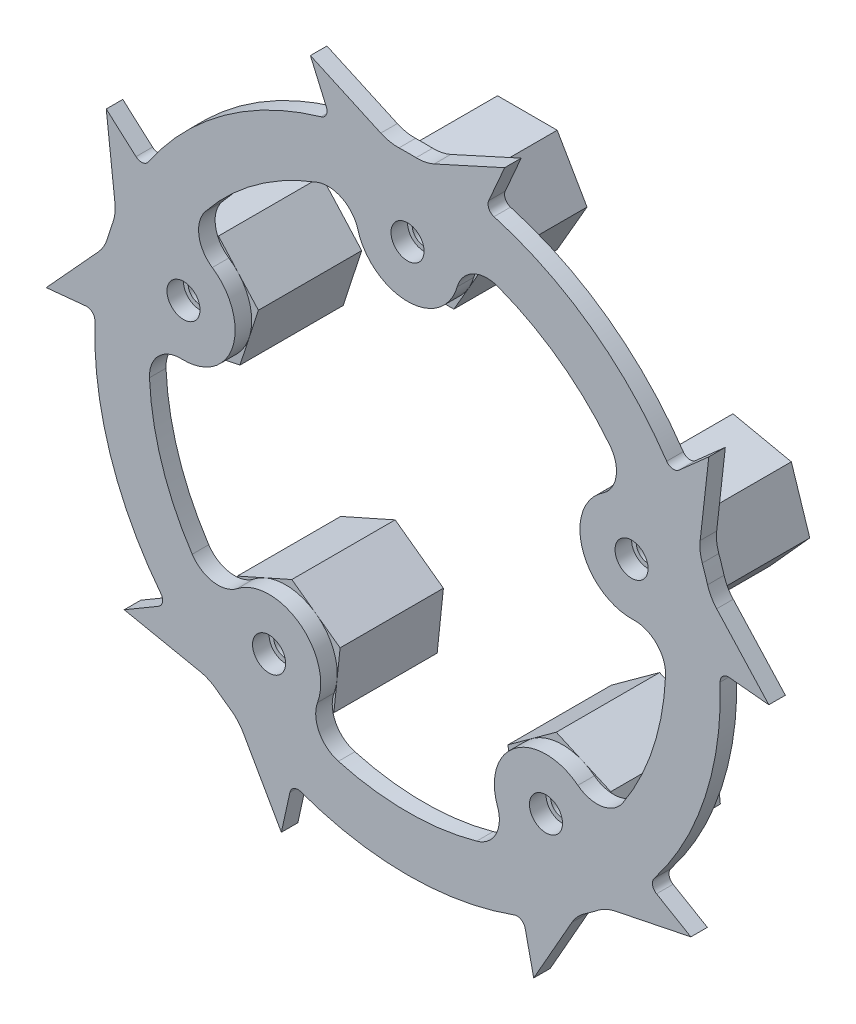
SolidWorks part; units mm, degrees
material "Alloy Steel (SS)"
ref_plane "Front Plane" through (0, 0, 0) normal (0, 0, 1) x (1, 0, 0)
ref_plane "Top Plane" through (0, 0, 0) normal (0, 1, 0) x (1, 0, 0)
ref_plane "Right Plane" through (0, 0, 0) normal (1, 0, 0) x (0, 0, -1)
sketch "Sketch1" plane through (0, 0, 0) normal (0, 0, 1) x (1, 0, 0)
  line L0 (0, 0) -> (0, 28.956) construction
  line L1 (0, 0) -> (27.5388, 8.9479) construction
  line L2 (0, 0) -> (17.0199, -23.4259) construction
  line L3 (0, 0) -> (-17.0199, -23.4259) construction
  line L4 (0, 0) -> (-27.5388, 8.9479) construction
  line L5 (-9.5106, 37.2552) -> (-11.938, 42.8169)
  line L6 (-11.938, 42.8169) -> (0, 0) construction
  line L7 (-11.938, 42.8169) -> (-3.2859, 38.8883)
  line L8 (0, 0) -> (0, 44.45) construction
  line L9 (9.5106, 37.2552) -> (11.938, 42.8169)
  line L10 (11.938, 42.8169) -> (3.2859, 38.8883)
  line L11 (-10.3266, 37.0373) -> (13.7805, 43.7588) construction
  line L12 (-11.938, 42.8169) -> (-5.2343, 44.686) construction
  circle A0 centre (0, 0) radius 44.45 construction
  circle A1 centre (0, 0) radius 31.75
  circle A2 centre (0, 28.956) radius 2.032
  arc A3 (6.1076, 27.2181) -> (-6.1076, 27.2181) centre (0, 28.956) cw
  arc A4 (6.1076, 27.2181) -> (11.1046, 29.7447) centre (9.7721, 26.1754) cw
  arc A5 (-6.1076, 27.2181) -> (-11.1046, 29.7447) centre (-9.7721, 26.1754) ccw
  arc A6 (23.9986, 14.2195) -> (24.8574, 19.7528) centre (21.8745, 17.3824) ccw
  arc A7 (27.7733, 2.6022) -> (23.9986, 14.2195) centre (27.5388, 8.9479) cw
  circle A8 centre (27.5388, 8.9479) radius 2.032
  arc A9 (27.7733, 2.6022) -> (31.7204, -1.3695) centre (27.914, -1.2052) cw
  arc A10 (20.9395, -18.43) -> (26.4674, -17.5369) centre (23.2913, -15.4324) ccw
  arc A11 (11.0573, -25.6098) -> (20.9395, -18.43) centre (17.0199, -23.4259) cw
  circle A12 centre (17.0199, -23.4259) radius 2.032
  arc A13 (11.0573, -25.6098) -> (8.4997, -30.5911) centre (7.4797, -26.9202) cw
  arc A14 (-11.0573, -25.6098) -> (-8.4997, -30.5911) centre (-7.4797, -26.9202) ccw
  arc A15 (-20.9395, -18.43) -> (-11.0573, -25.6098) centre (-17.0199, -23.4259) cw
  circle A16 centre (-17.0199, -23.4259) radius 2.032
  arc A17 (-20.9395, -18.43) -> (-26.4674, -17.5369) centre (-23.2913, -15.4324) cw
  arc A18 (-27.7733, 2.6022) -> (-31.7204, -1.3695) centre (-27.914, -1.2052) ccw
  arc A19 (-23.9986, 14.2195) -> (-27.7733, 2.6022) centre (-27.5388, 8.9479) cw
  circle A20 centre (-27.5388, 8.9479) radius 2.032
  arc A21 (-23.9986, 14.2195) -> (-24.8574, 19.7528) centre (-21.8745, 17.3824) cw
  circle A22 centre (0, 0) radius 38.45
  arc A23 (-3.2859, 38.8883) -> (-1.0473, 38.4357) centre (-1.1856, 43.5139) ccw
  arc A24 (3.2859, 38.8883) -> (1.0473, 38.4357) centre (1.1856, 43.5139) cw
  point P47 (0, 0)
  point P57 (4.3937, 27.6917)
  dimension "D1" = 88.9
  dimension "D2" = 63.5
  dimension "D3" = 4.064
  dimension "D4" = 28.956
  dimension "D6" = 6.35
  dimension "D8" = 6
  dimension "D12" = 5.08
  dimension "D10" = 40
  dimension "D7" = 3.81
  dimension "D9" = 8
  dimension "D11" = 23.876
  dimension "D5" = 5
extrude "Boss-Extrude1" add sketch "Sketch1" along normal blind 2.032 contours A0 A1 | A19 A21 A1 A18 A20 | A5 A3 A4 A1 A2 | A7 A9 A1 A6 A8 | A11 A13 A1 A10 A12 | A15 A17 A1 A14 A16 region at (-5.1616, 37.0042, 0) region at (31.719, -0.6844, 0) region at (7.9446, 29.7898, 0) region at (18.53, -25.5044, 0) region at (-25.8728, 16.7619, 0) region at (-18.53, -25.5044, 0)
extrude "Boss-Extrude5" add sketch "Sketch1<5>" along normal up to surface (2.032 mm away) contours L7 L5 A22 | A22 L9 L10 region at (-7.9331, 39.5489, 0) region at (7.9331, 39.5489, 0) up to face at (0, 0, 2.032)
sketch "Sketch1<5>" plane through (0, 0, 0) normal (0, 0, 1) x (1, 0, 0) same geometry as "Sketch1"
fillet "Fillet2" radius 1.016 2 edges at (9.5106, 37.2552, 1.016) (-9.5106, 37.2552, 1.016)
pattern_circular "CirPattern2" count 5 over 360 about axis through (0, 0, 2.032) along (0, 0, 1) of "Boss-Extrude5", "Fillet2"
sketch "Sketch2" plane through (0, 0, 0) normal (0, 0, 1) x (1, 0, 0)
  line L1 (7.3323, 28.956) -> (3.6662, 35.306)
  line L2 (3.6662, 35.306) -> (-3.6662, 35.306)
  line L3 (-3.6662, 35.306) -> (-7.3323, 28.956)
  line L4 (-7.3323, 28.956) -> (-3.6662, 22.606)
  line L5 (-3.6662, 22.606) -> (3.6662, 22.606)
  line L6 (3.6662, 22.606) -> (7.3323, 28.956)
  circle A0 centre (0, 28.956) radius 6.35 construction
  circle A1 centre (0, 28.956) radius 1.4641
  dimension "D1" = 12.7
extrude "Boss-Extrude6" add sketch "Sketch2" against normal blind 12.7 separate body
pattern_circular "CirPattern3" count 5 over 360 about axis through (0, 0, 2.032) along (0, 0, -1) reverse direction yes of bodies 104
